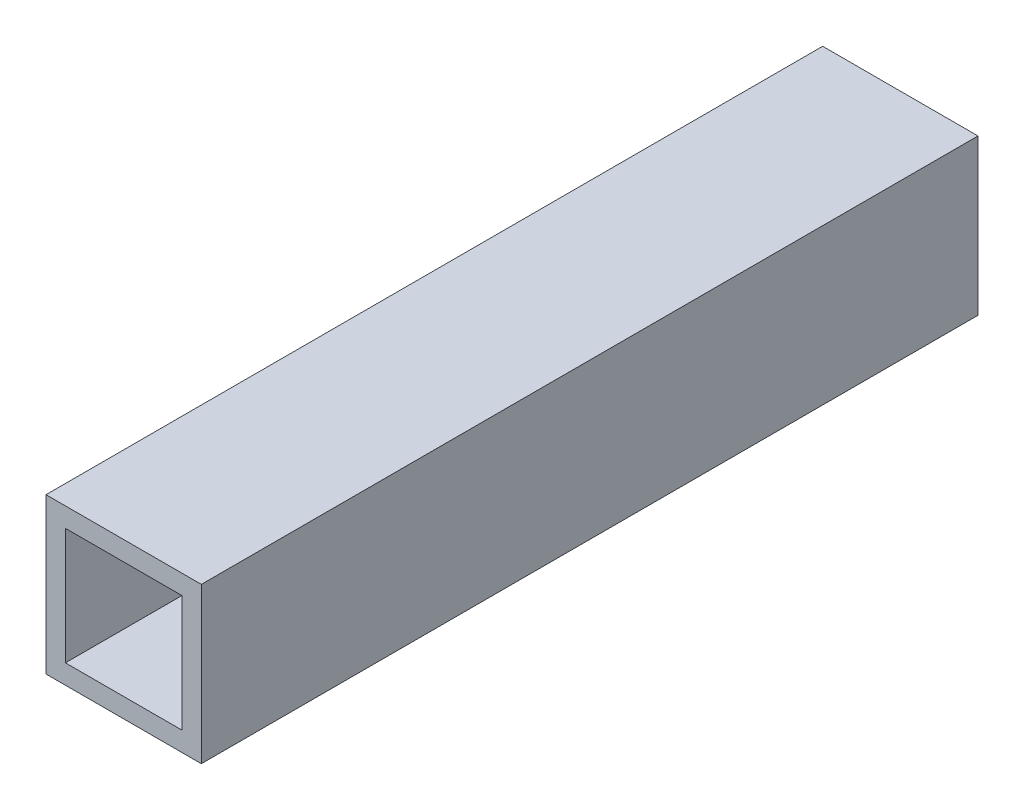
SolidWorks part; units mm, degrees
ref_plane "Front Plane" through (0, 0, 0) normal (0, 0, 1) x (1, 0, 0)
ref_plane "Top Plane" through (0, 0, 0) normal (0, 1, 0) x (1, 0, 0)
ref_plane "Right Plane" through (0, 0, 0) normal (1, 0, 0) x (0, 0, -1)
sketch "Sketch1" plane through (0, 0, 0) normal (0, 0, 1) x (1, 0, 0)
  line L1 (-12.7, -12.7) -> (12.7, -12.7)
  line L2 (-12.7, -12.7) -> (-12.7, 12.7)
  line L3 (-12.7, 12.7) -> (12.7, 12.7)
  line L4 (12.7, -12.7) -> (12.7, 12.7)
  line L5 (-12.7, -12.7) -> (12.7, 12.7) construction
  line L6 (-12.7, 12.7) -> (12.7, -12.7) construction
  point P0 (0, 0)
  dimension "D1" = 25.4
  dimension "D2" = 25.4
extrude "Boss-Extrude1" add sketch "Sketch1" along normal mid plane 127
shell "Shell1" thickness 3.175 removed face at (0, 0, -63.5) removed face at (0, 0, 63.5)
